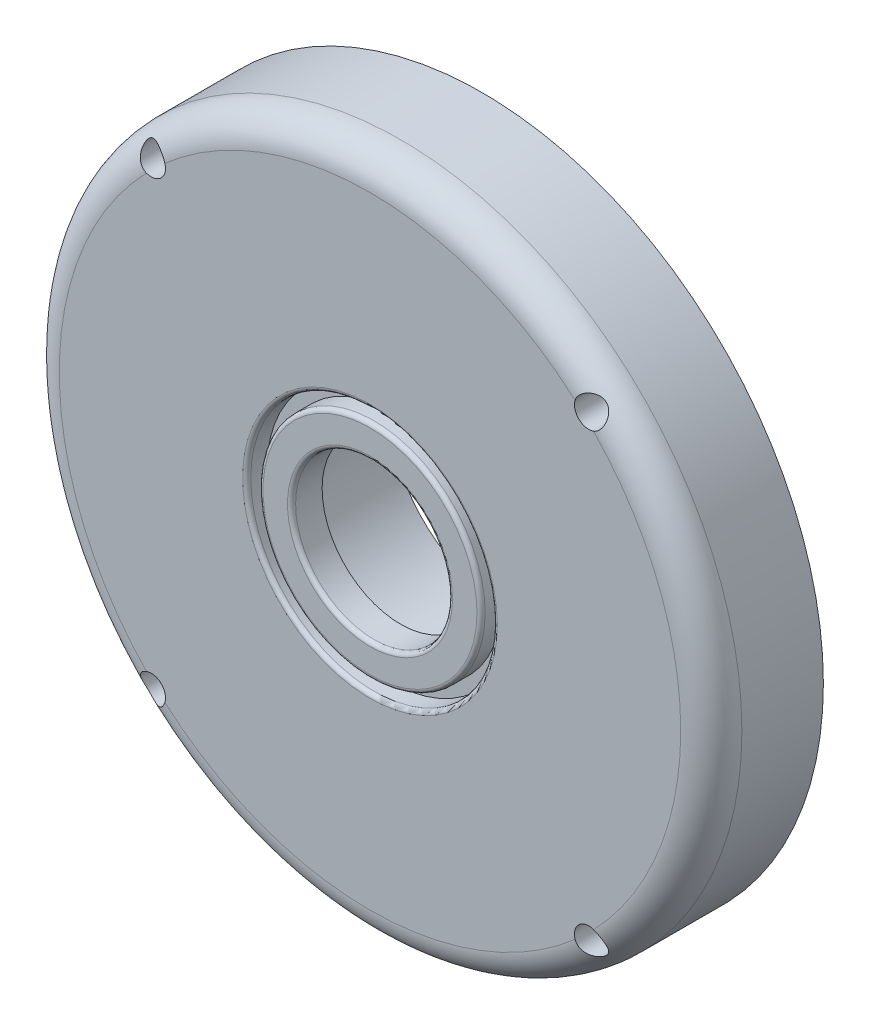
SolidWorks part; units mm, degrees
ref_plane "Front" through (0, 0, 0) normal (0, 0, 1) x (1, 0, 0)
ref_plane "Top" through (0, 0, 0) normal (0, 1, 0) x (1, 0, 0)
ref_plane "Right" through (0, 0, 0) normal (1, 0, 0) x (0, 0, -1)
sketch "Çizim1" plane through (0, 0, 0) normal (0, 0, 1) x (1, 0, 0)
  circle A0 centre (0, 0) radius 148
  dimension "D1" = 296
extrude "Yükseklik-Ekstrüzyon1" add sketch "Çizim1" along normal blind 60
sketch "Çizim2" plane through (0, 0, 0) normal (0, 0, 1) x (1, 0, 0)
  circle A1 centre (0, 0) radius 167.5
  dimension "D1" = 335
extrude "Yükseklik-Ekstrüzyon2" add sketch "Çizim2" along normal blind 50 from offset 10
sketch "Çizim3" plane through (0, 0, 0) normal (0, 0, -1) x (-1, 0, 0)
  circle A0 centre (0, 0) radius 55
  dimension "D1" = 110
extrude "Kes-Ekstrüzyon1" cut sketch "Çizim3" against normal blind 741
sketch "Çizim4" plane through (0, 0, 0) normal (0, 0, -1) x (-1, 0, 0)
  circle A0 centre (0, 0) radius 55
  circle A1 centre (0, 0) radius 38.5
  dimension "D1" = 77
  dimension "D2" = 110
extrude "Yükseklik-Ekstrüzyon3" add sketch "Çizim4" against normal up to surface (60 mm away) from offset 50 up to face at (55, 0, 60) offset against normal yes
sketch "Çizim5" plane through (0, 0, 60) normal (0, 0, 1) x (1, 0, 0)
  circle A0 centre (0, 0) radius 38.5 construction
  circle A1 centre (0, 0) radius 167.5
  circle A2 centre (0, 0) radius 167.5
  circle A3 centre (0, 0) radius 38.5
  dimension "D1" = 0
extrude "Yükseklik-Ekstrüzyon4" add sketch "Çizim5" along normal blind 5
sketch "Çizim6" plane through (0, 0, 65) normal (0, 0, 1) x (1, 0, 0)
  circle A0 centre (0, 0) radius 54.5
  circle A1 centre (0, 0) radius 60.5
  dimension "D1" = 109
  dimension "D2" = 121
extrude "Kes-Ekstrüzyon2" cut sketch "Çizim6" against normal blind 10
sketch "Çizim7" plane through (0, 0, 65) normal (0, 0, 1) x (1, 0, 0)
  line L5 (107.3499, -112.5) -> (-107.3499, -112.5) construction
  line L6 (107.3499, -112.5) -> (107.3499, 112.5) construction
  line L7 (107.3499, 112.5) -> (-107.3499, 112.5) construction
  line L8 (-107.3499, -112.5) -> (-107.3499, 112.5) construction
  line L9 (107.3499, -112.5) -> (-107.3499, 112.5) construction
  line L10 (107.3499, 112.5) -> (-107.3499, -112.5) construction
  circle A1 centre (0, 0) radius 155.5 construction
  circle A2 centre (-107.3499, 112.5) radius 4
  circle A3 centre (107.3499, 112.5) radius 4
  circle A4 centre (107.3499, -112.5) radius 4
  circle A5 centre (-107.3499, -112.5) radius 4
  dimension "D1" = 311
  dimension "D3" = 8
  dimension "D2" = 225
extrude "Kes-Ekstrüzyon3" cut sketch "Çizim7" against normal up to surface (55 mm away) up to face at (148, 0, 10)
sketch "Çizim8" plane through (0, 0, 65) normal (0, 0, 1) x (1, 0, 0)
  circle A0 centre (-107.3499, 112.5) radius 7
  circle A1 centre (107.3499, 112.5) radius 7
  circle A2 centre (107.3499, -112.5) radius 7
  circle A3 centre (-107.3499, -112.5) radius 7
  dimension "D1" = 14
extrude "Kes-Ekstrüzyon4" cut sketch "Çizim8" against normal blind 17
fillet "Radyus1" radius 15 1 edges at (167.5, 0, 65)
fillet "Radyus2" radius 2 3 edges at (60.5, 0, 65) (54.5, 0, 65) (38.5, 0, 65)
